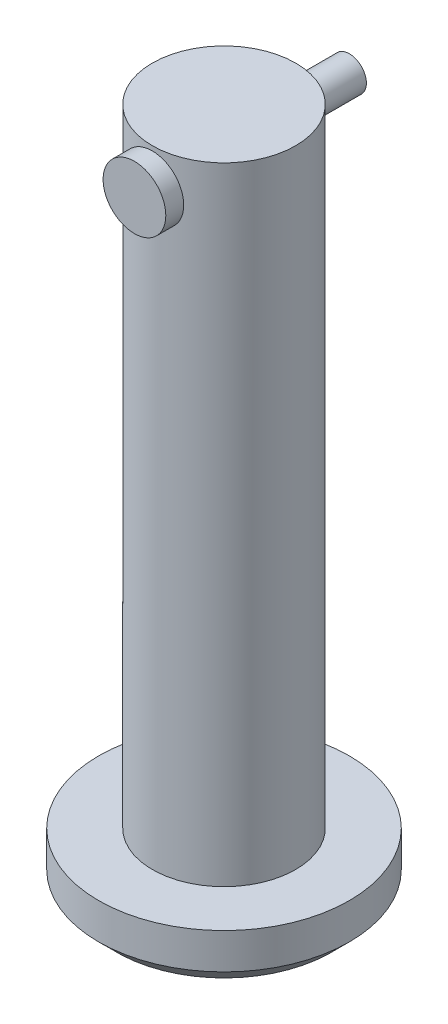
SolidWorks part; units mm, degrees
ref_plane "Front Plane" through (0, 0, 0) normal (0, 0, 1) x (1, 0, 0)
ref_plane "Top Plane" through (0, 0, 0) normal (0, 1, 0) x (1, 0, 0)
ref_plane "Right Plane" through (0, 0, 0) normal (1, 0, 0) x (0, 0, -1)
sketch "Sketch1" plane through (0, 0, 0) normal (0, 1, 0) x (1, 0, 0)
  circle A0 centre (0, 0) radius 4
extrude "Boss-Extrude1" add sketch "Sketch1" along normal blind 35
sketch "Sketch2" plane through (0, 0, 0) normal (0, -1, 0) x (1, 0, 0)
  circle A0 centre (0, 0) radius 7
  dimension "D1" = 14
extrude "Boss-Extrude2" add sketch "Sketch2" along normal blind 3
chamfer "Chamfer1" distance 1 angle 45 1 edges at (0, -3, -7)
sketch "Sketch3" plane through (0, 0, 0) normal (0, 0, 1) x (1, 0, 0)
  line L0 (4, 35) -> (-4, 35) construction
  circle A0 centre (0, 33) radius 1
  dimension "D1" = 2
  dimension "D2" = 2
extrude "Cut-Extrude1" cut sketch "Sketch3" against normal blind 10 and the other way blind 10
sketch "Sketch4" plane through (0, 0, 0) normal (0, 0, 1) x (1, 0, 0)
  circle A0 centre (0, 33) radius 0.95
  dimension "D1" = 1.9
extrude "Boss-Extrude3" add sketch "Sketch4" along normal blind 5 and the other way blind 7 separate body
sketch "Sketch5" plane through (0, 0, 5) normal (0, 0, 1) x (1, 0, 0)
  circle A0 centre (0, 33) radius 1.75
  dimension "D1" = 3.5
extrude "Boss-Extrude4" add sketch "Sketch5" against normal blind 1
